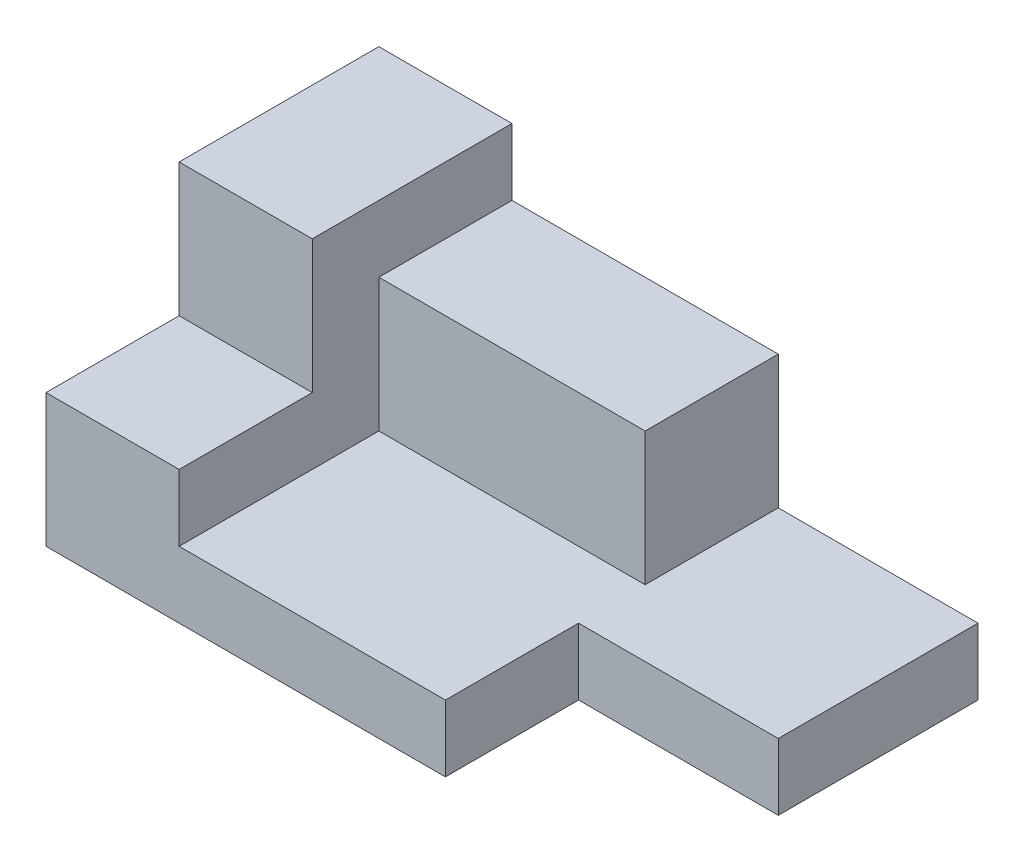
SolidWorks part; units mm, degrees
ref_plane "Front Plane" through (0, 0, 0) normal (0, 0, 1) x (1, 0, 0)
ref_plane "Top Plane" through (0, 0, 0) normal (0, 1, 0) x (1, 0, 0)
ref_plane "Right Plane" through (0, 0, 0) normal (1, 0, 0) x (0, 0, -1)
sketch "Sketch2" plane through (0, 0, 0) normal (0, 1, 0) x (1, 0, 0)
  line L0 (20, 20) -> (20, 0)
  line L1 (0, 0) -> (60, 0)
  line L2 (0, 0) -> (0, 50)
  line L3 (0, 50) -> (60, 50)
  line L4 (60, 0) -> (60, 50)
  line L5 (60, 50) -> (90, 50)
  line L6 (60, 50) -> (60, 20)
  line L7 (60, 20) -> (90, 20)
  line L8 (90, 50) -> (90, 20)
  line L9 (60, 50) -> (20, 50)
  line L10 (60, 50) -> (60, 30)
  line L11 (60, 30) -> (20, 30)
  line L12 (20, 50) -> (20, 30)
  line L13 (0, 50) -> (20, 50)
  line L14 (0, 50) -> (0, 20)
  line L15 (0, 20) -> (20, 20)
  line L16 (20, 50) -> (20, 20)
  dimension "D1" = 50
  dimension "D2" = 60
  dimension "D3" = 30
  dimension "D4" = 30
  dimension "D5" = 20
  dimension "D6" = 40
  dimension "D7" = 30
extrude "Boss-Extrude1" add sketch "Sketch2" along normal blind 10 contours L8 L5 L6 L4 L7 | L3 L12 L11 L6 | L16 L12 L3 L2 L15 | L11 L16 L0 L1 L4 | L15 L2 L1 L0 region at (40, 0, -15) region at (10, 0, -10) region at (10, 0, -35) region at (40, 0, -40) region at (75, 0, -35)
extrude "Boss-Extrude2" add sketch "Sketch2<3>" along normal blind 20 from surface contours L3 L12 L11 L6 region at (40, 0, -40) starting at face at (50, 10, -23.3333)
sketch "Sketch2<3>" plane through (0, 0, 0) normal (0, 1, 0) x (1, 0, 0) same geometry as "Sketch2"
extrude "Boss-Extrude3" add sketch "Sketch2<4>" along normal blind 30 from surface contours L16 L12 L3 L2 L15 region at (10, 0, -35) starting at face at (46, 10, -30)
sketch "Sketch2<4>" plane through (0, 0, 0) normal (0, 1, 0) x (1, 0, 0) same geometry as "Sketch2"
extrude "Boss-Extrude4" add sketch "Sketch2<5>" along normal blind 10 from surface contours L15 L2 L1 L0 region at (10, 0, -10) starting at face at (46, 10, -24)
sketch "Sketch2<5>" plane through (0, 0, 0) normal (0, 1, 0) x (1, 0, 0) same geometry as "Sketch2"
